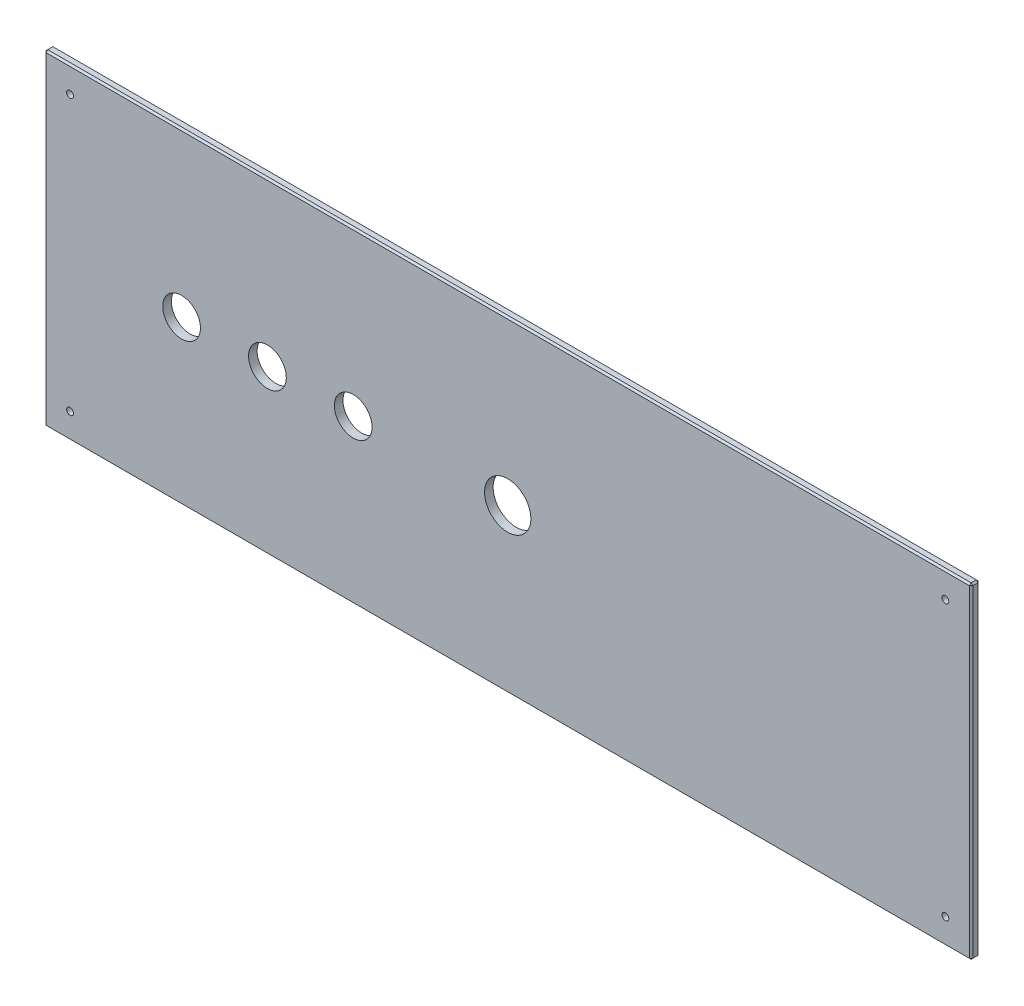
SolidWorks part; units mm, degrees
material "ABS"
ref_plane "Front Plane" through (0, 0, 0) normal (0, 0, 1) x (1, 0, 0)
ref_plane "Top Plane" through (0, 0, 0) normal (0, 1, 0) x (1, 0, 0)
ref_plane "Right Plane" through (0, 0, 0) normal (1, 0, 0) x (0, 0, -1)
sketch "Sketch1" plane through (0, 0, 0) normal (0, 0, 1) x (1, 0, 0)
  line L1 (0, 0) -> (540, 0)
  line L2 (0, 0) -> (0, 190)
  line L3 (0, 190) -> (540, 190)
  line L4 (540, 0) -> (540, 190)
  dimension "D1" = 540
  dimension "D2" = 190
extrude "Boss-Extrude1" add sketch "Sketch1" along normal blind 5
chamfer "Chamfer1" distance 1 angle 45 12 edges at (270, 0, 0) (540, 95, 0) (270, 190, 0) (0, 95, 0) (270, 190, 5) (0, 190, 2.5) (0, 95, 5) (0, 0, 2.5) (270, 0, 5) (540, 0, 2.5) (540, 95, 5) (540, 190, 2.5)
sketch "Sketch2" plane through (0, 0, 5) normal (0, 0, 1) x (1, 0, 0)
  line L0 (1, 190) -> (539, 190) construction
  line L1 (15, 175) -> (525, 175) construction
  line L2 (15, 175) -> (15, 15) construction
  line L3 (15, 15) -> (525, 15) construction
  line L4 (525, 175) -> (525, 15) construction
  line L5 (540, 189) -> (540, 1) construction
  line L6 (539, 0) -> (1, 0) construction
  line L7 (0, 1) -> (0, 189) construction
  circle A0 centre (525, 175) radius 2
  circle A1 centre (525, 15) radius 2
  circle A2 centre (15, 175) radius 2
  circle A3 centre (15, 15) radius 2
  dimension "D5" = 4
  dimension "D6" = 4
  dimension "D7" = 4
  dimension "D8" = 4
  dimension "D1" = 15
  dimension "D2" = 15
  dimension "D3" = 15
  dimension "D4" = 15
extrude "Cut-Extrude1" cut sketch "Sketch2" against normal blind 5
sketch "Sketch3" plane through (0, 0, 5) normal (0, 0, 1) x (1, 0, 0)
  line L0 (270, 189) -> (270, 1) construction
  line L1 (213, 119) -> (327, 119)
  line L2 (213, 119) -> (213, 71)
  line L3 (213, 71) -> (327, 71)
  line L4 (327, 119) -> (327, 71)
  line L5 (539, 189) -> (1, 189) construction
  line L6 (1, 1) -> (539, 1) construction
  line L7 (1, 95) -> (539, 95) construction
  line L8 (1, 189) -> (1, 1) construction
  line L9 (539, 1) -> (539, 189) construction
  dimension "D1" = 114
  dimension "D2" = 48
  dimension "D3" = 57
  dimension "D4" = 24
sketch "Sketch4" plane through (0, 0, 5) normal (0, 0, 1) x (1, 0, 0)
  line L0 (1, 95) -> (539, 95) construction
  line L1 (1, 189) -> (1, 1) construction
  line L2 (539, 1) -> (539, 189) construction
  line L3 (0, 1) -> (0, 189) construction
  circle A0 centre (80, 95) radius 11
  circle A1 centre (130, 95) radius 11
  circle A2 centre (180, 95) radius 11
  circle A3 centre (270, 95) radius 13.5
  dimension "D1" = 27
  dimension "D2" = 22
  dimension "D3" = 22
  dimension "D4" = 22
  dimension "D5" = 50
  dimension "D6" = 50
  dimension "D7" = 80
extrude "Cut-Extrude2" cut sketch "Sketch4" against normal blind 10
sketch "Sketch5" plane through (0, 0, 0) normal (0, 0, -1) x (-1, 0, 0)
  line L0 (-180, 95) -> (-180, 120) construction
  line L1 (-195, 130) -> (-165, 130)
  line L2 (-195, 130) -> (-195, 120)
  line L3 (-195, 120) -> (-165, 120)
  line L4 (-165, 130) -> (-165, 120)
  line L5 (-145, 130) -> (-115, 130)
  line L6 (-145, 130) -> (-145, 120)
  line L7 (-145, 120) -> (-115, 120)
  line L8 (-115, 130) -> (-115, 120)
  line L9 (-95, 130) -> (-65, 130)
  line L10 (-95, 130) -> (-95, 120)
  line L11 (-95, 120) -> (-65, 120)
  line L12 (-65, 130) -> (-65, 120)
  line L13 (-270, 95) -> (-270, 120) construction
  line L14 (-285, 130) -> (-255, 130)
  line L15 (-285, 130) -> (-285, 120)
  line L16 (-285, 120) -> (-255, 120)
  line L17 (-255, 130) -> (-255, 120)
  line L18 (-270, 70) -> (-270, 95) construction
  line L19 (-297.5, 70) -> (-242.5, 70)
  line L20 (-297.5, 70) -> (-297.5, 60)
  line L21 (-297.5, 60) -> (-242.5, 60)
  line L22 (-242.5, 70) -> (-242.5, 60)
  dimension "D1" = 30
  dimension "D2" = 30
  dimension "D3" = 30
  dimension "D4" = 10
  dimension "D5" = 10
  dimension "D6" = 10
  dimension "D7" = 50
  dimension "D8" = 50
  dimension "D9" = 25
  dimension "D10" = 30
  dimension "D11" = 10
  dimension "D12" = 55
  dimension "D13" = 25
extrude "Cut-Extrude3" cut sketch "Sketch5" against normal blind 0.5
chamfer "Chamfer2" distance 0.5 angle 45 20 edges at (80, 130, 0.5) (65, 125, 0.5) (80, 120, 0.5) (95, 125, 0.5) (130, 130, 0.5) (115, 125, 0.5) (145, 125, 0.5) (130, 120, 0.5) (180, 130, 0.5) (165, 125, 0.5) (180, 120, 0.5) (195, 125, 0.5) (270, 70, 0.5) (242.5, 65, 0.5) (270, 60, 0.5) (297.5, 65, 0.5) (270, 130, 0.5) (285, 125, 0.5) (270, 120, 0.5) (255, 125, 0.5)
sketch "Sketch6" plane through (0, 0, 0.5) normal (0, 0, -1) x (-1, 0, 0)
  text T0 "AURORA" font "Century Gothic" height 3.5
extrude "Cut-Extrude4" cut sketch "Sketch6" against normal blind 0.5
sketch "Sketch7" plane through (0, 0, 0.5) normal (0, 0, -1) x (-1, 0, 0)
  text T0 "ARDUINO" font "Century Gothic" height 3.5
extrude "Cut-Extrude5" cut sketch "Sketch7" against normal blind 0.5
sketch "Sketch8" plane through (0, 0, 0.5) normal (0, 0, -1) x (-1, 0, 0)
  text T0 "DAQ"
extrude "Cut-Extrude6" cut sketch "Sketch8" against normal blind 0.5
sketch "Sketch10" plane through (0, 0, 0.5) normal (0, 0, -1) x (-1, 0, 0)
  text T0 "ARDUINO" font "Century Gothic" height 3.5
extrude "Cut-Extrude7" cut sketch "Sketch10" against normal blind 0.5
sketch "Sketch11" plane through (0, 0, 0.5) normal (0, 0, -1) x (-1, 0, 0)
  text T0 "PROGRAMMING" font "Century Gothic" height 3.5
extrude "Cut-Extrude8" cut sketch "Sketch11" against normal blind 0.5
